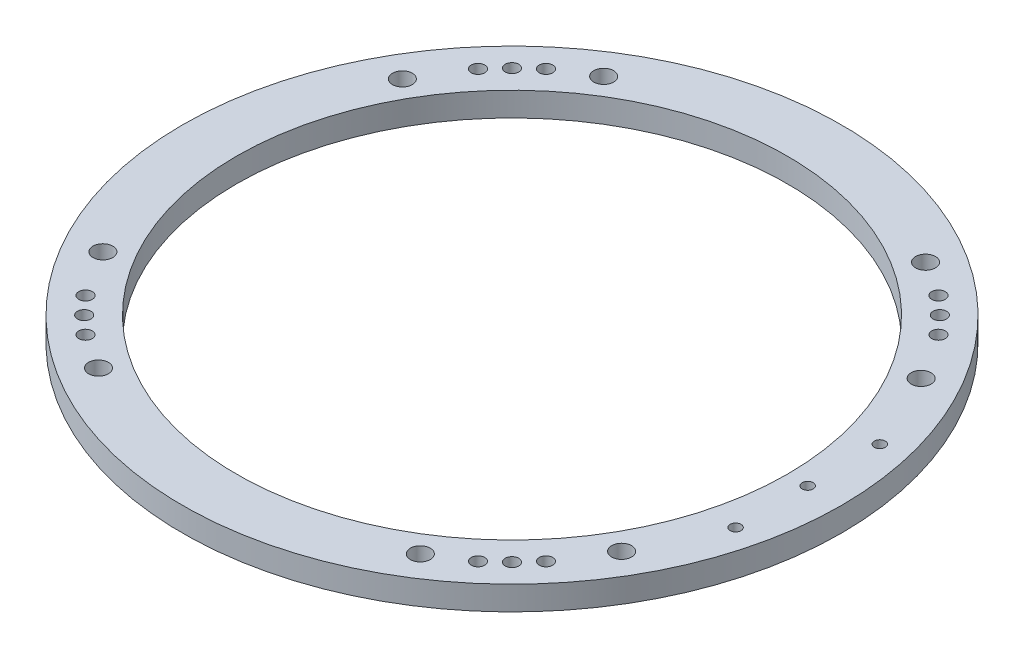
SolidWorks part; units mm, degrees
material "Oak"
ref_plane "Front Plane" through (0, 0, 0) normal (0, 0, 1) x (1, 0, 0)
ref_plane "Top Plane" through (0, 0, 0) normal (0, 1, 0) x (1, 0, 0)
ref_plane "Right Plane" through (0, 0, 0) normal (1, 0, 0) x (0, 0, -1)
sketch "Sketch1" plane through (0, 0, 0) normal (0, 0, 1) x (1, 0, 0)
  line L0 (0, 1125.8152) -> (0, -48874.1848) construction
  line L1 (145.5262, 1052.195) -> (152.4, 1052.195)
  line L9 (145.5262, 1064.895) -> (174.1012, 1064.895)
  line L10 (145.5262, 1064.895) -> (145.5262, 1052.195)
  line L11 (145.5262, 1052.195) -> (174.1012, 1052.195)
  line L12 (174.1012, 1064.895) -> (174.1012, 1052.195)
revolve "Revolve1" add sketch "Sketch1" angle 360 about L0 region at (159.8137, 1058.545, 0)
hole_wizard "9/32 (0.28125) Diameter Hole1" positions "Sketch9" profile "Sketch10" hole size "9/32" standard "ANSI Inch" end condition through all
sketch "Sketch9" plane through (0, 1052.195, 0) normal (0, -1, 0) x (-1, 0, 0)
  line L0 (0, 0) -> (113.0054, 113.0054) construction
  line L3 (0, 0) -> (103.6677, 121.6282) construction
  arc A0 (103.6677, 121.6282) -> (121.6282, 103.6677) centre (0, 0) cw
  circle A1 centre (0, 0) radius 159.8137 construction
  point P0 (103.6677, 121.6282)
  point P2 (121.6282, 103.6677)
  point P15 (113.0054, 113.0054)
sketch "Sketch10" plane through (-103.6677, 1052.195, -121.6282) normal (1, 0, 0) x (0, 0, -1)
  line L0 (0, 0) -> (0, 12.7)
  line L1 (0, 12.7) -> (3.5719, 12.7)
  line L2 (3.5719, 12.7) -> (3.5719, 0)
  line L5 (3.5719, 0) -> (0, 0)
  line L11 (0, -6.35) -> (0, 107.95) construction
  dimension "Thru Hole Dia." = 7.1437
  dimension "Thru Hole Depth" = 12.7
pattern_circular "CirPattern1" count 4 over 360 about axis through (0, 1125.8152, 0) along (0, 1, 0) of "9/32 (0.28125) Diameter Hole1"
ref_plane "Plane1" through (0, 1058.545, 0) normal (0, 1, 0) x (1, 0, 0)
hole_wizard "M5 Clearance Hole1" positions "Sketch14" profile "Sketch15" hole size "M5" standard "ANSI Metric" end condition through all
sketch "Sketch14" plane through (0, 1064.895, 0) normal (0, 1, 0) x (1, 0, 0)
  point P9 (156.21, -38.1)
  point P12 (156.21, 0)
  point P14 (156.21, 38.1)
sketch "Sketch15" plane through (156.21, 1064.895, 38.1) normal (1, 0, 0) x (0, 0, 1)
  line L0 (0, 0) -> (0, 12.7)
  line L1 (0, 12.7) -> (2.9, 12.7)
  line L2 (2.9, 12.7) -> (2.9, 0)
  line L5 (2.9, 0) -> (0, 0)
  line L11 (0, -6.35) -> (0, 107.95) construction
  dimension "Thru Hole Dia." = 5.8
  dimension "Thru Hole Depth" = 12.7
hole_wizard "Z (0.413) Diameter Hole1" positions "Sketch16" profile "Sketch17" hole size "Z" standard "ANSI Inch" end condition through all
sketch "Sketch16" plane through (0, 1064.895, 0) normal (0, 1, 0) x (1, 0, 0)
  line L0 (-137.0279, -79.1131) -> (137.0279, 79.1131) construction
  line L4 (137.0279, -79.1131) -> (-137.0279, 79.1131) construction
  line L6 (0, 0) -> (0, 158.2262) construction
  line L8 (-85.0149, -133.4467) -> (85.0149, 133.4467) construction
  line L11 (-85.0149, 133.4467) -> (85.0149, -133.4467) construction
  circle A0 centre (0, 0) radius 158.2262 construction
  circle A1 centre (0, 0) radius 145.5262 construction
  point P0 (-137.0279, -79.1131)
  point P2 (137.0279, -79.1131)
  point P4 (137.0279, 79.1131)
  point P6 (-137.0279, 79.1131)
  point P37 (-85.0149, 133.4467)
  point P39 (85.0149, 133.4467)
  point P41 (85.0149, -133.4467)
  point P43 (-85.0149, -133.4467)
  dimension "D2" = 12.7
  dimension "D1" = 120
  dimension "D3" = 65
sketch "Sketch17" plane through (-137.0279, 1064.895, 79.1131) normal (1, 0, 0) x (0, 0, 1)
  line L0 (0, 0) -> (0, 12.7)
  line L1 (0, 12.7) -> (5.2451, 12.7)
  line L2 (5.2451, 12.7) -> (5.2451, 0)
  line L5 (5.2451, 0) -> (0, 0)
  line L11 (0, -6.35) -> (0, 107.95) construction
  dimension "Thru Hole Dia." = 10.4902
  dimension "Thru Hole Depth" = 12.7
sketch "Sketch18" plane through (0, 1064.895, 0) normal (0, 1, 0) x (1, 0, 0)
  circle A5 centre (-103.6677, 121.6282) radius 1.5875
  circle A6 centre (-113.0054, 113.0054) radius 1.5875
  circle A7 centre (-121.6282, 103.6677) radius 1.5875
  circle A10 centre (103.6677, 121.6282) radius 1.5875
  circle A11 centre (113.0054, 113.0054) radius 1.5875
  circle A12 centre (121.6282, 103.6677) radius 1.5875
  circle A14 centre (-121.6282, -103.6677) radius 1.5875
  circle A37 centre (-113.0054, -113.0054) radius 1.5875
  circle A38 centre (-103.6677, -121.6282) radius 1.5875
  circle A39 centre (103.6677, -121.6282) radius 1.5875
  circle A40 centre (113.0054, -113.0054) radius 1.5875
  circle A41 centre (121.6282, -103.6677) radius 1.5875
  circle A53 centre (103.6677, 121.6282) radius 3.5719
  circle A54 centre (103.6677, 121.6282) radius 3.5719
  circle A55 centre (113.0054, 113.0054) radius 3.5719
  circle A56 centre (113.0054, 113.0054) radius 3.5719
  circle A57 centre (103.6677, -121.6282) radius 3.5719
  circle A58 centre (103.6677, -121.6282) radius 3.5719
  circle A59 centre (-121.6282, -103.6677) radius 3.5719
  circle A60 centre (-121.6282, -103.6677) radius 3.5719
  circle A61 centre (-103.6677, -121.6282) radius 3.5719
  circle A62 centre (-103.6677, -121.6282) radius 3.5719
  circle A63 centre (-113.0054, -113.0054) radius 3.5719
  circle A64 centre (-113.0054, -113.0054) radius 3.5719
  circle A65 centre (-103.6677, 121.6282) radius 3.5719
  circle A66 centre (-103.6677, 121.6282) radius 3.5719
  circle A67 centre (-121.6282, 103.6677) radius 3.5719
  circle A68 centre (-121.6282, 103.6677) radius 3.5719
  circle A69 centre (-113.0054, 113.0054) radius 3.5719
  circle A70 centre (-113.0054, 113.0054) radius 3.5719
  circle A73 centre (113.0054, -113.0054) radius 3.5719
  circle A74 centre (113.0054, -113.0054) radius 3.5719
  circle A75 centre (121.6282, -103.6677) radius 3.5719
  circle A76 centre (121.6282, -103.6677) radius 3.5719
  circle A77 centre (121.6282, 103.6677) radius 3.5719
  circle A78 centre (121.6282, 103.6677) radius 3.5719
  dimension "D13" = 3.175
  dimension "D14" = 0
  dimension "D15" = 0
  dimension "D16" = 0
  dimension "D17" = 0
  dimension "D18" = 0
  dimension "D19" = 0
  dimension "D20" = 0
  dimension "D21" = 0
  dimension "D22" = 0
  dimension "D24" = 0
  dimension "D25" = 0
  dimension "D26" = 0
extrude "Boss-Extrude1" [suppressed] add sketch "Sketch18" against normal up to surface (12.7 mm away) up to face at (-137.0279, 1052.195, 84.3582)
